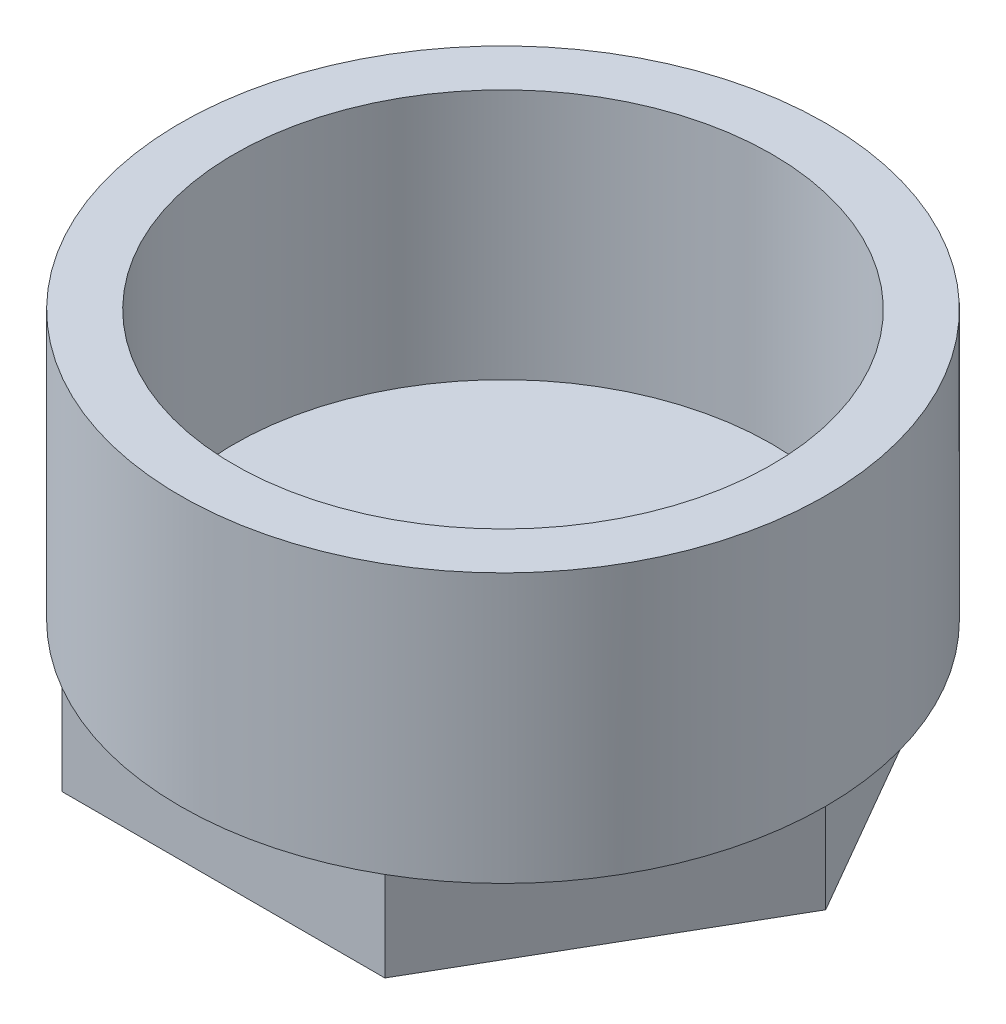
SolidWorks part; units mm, degrees
material "1.0035 (S185)"
ref_plane "Piano frontale" through (0, 0, 0) normal (0, 0, 1) x (1, 0, 0)
ref_plane "Piano superiore" through (0, 0, 0) normal (0, 1, 0) x (1, 0, 0)
ref_plane "Piano destro" through (0, 0, 0) normal (1, 0, 0) x (0, 0, -1)
sketch "Schizzo1" plane through (0, 0, 0) normal (0, 0, 1) x (1, 0, 0)
  line L0 (0, 0) -> (-18, 0)
  line L1 (-18, 0) -> (-18, 20)
  line L2 (-18, 20) -> (-15, 20)
  line L3 (-15, 20) -> (-15, 6)
  line L4 (-15, 6) -> (0, 6)
  line L5 (0, 6) -> (0, 0)
  line L6 (0, 0) -> (0, 10.8439) construction
  dimension "D1" = 36
  dimension "D2" = 30
  dimension "D3" = 6
  dimension "D4" = 20
revolve "Rivoluzione1" add sketch "Schizzo1" angle 360 about L6
sketch "Schizzo2" plane through (0, 0, 0) normal (0, -1, 0) x (1, 0, 0)
  circle A0 centre (0, 0) radius 1.585
  dimension "D1" = 3.17
extrude "Taglio-Estrusione1" cut sketch "Schizzo2" against normal blind 10
sketch "Schizzo3" plane through (0, 0, 0) normal (0, -1, 0) x (1, 0, 0)
  circle A0 centre (0, 0) radius 1.019
  circle A1 centre (0, 0) radius 1.5875
  dimension "D1" = 3.175
extrude "Estrusione-Estrusione1" [suppressed] add sketch "Schizzo3" along normal blind 8
sketch "Schizzo4" plane through (0, 0, 0) normal (0, 0, 1) x (1, 0, 0)
  line L0 (0, 0) -> (0, -9.8437)
sketch "Schizzo5" plane through (0, 0, 0) normal (0, -1, 0) x (-1, 0, 0)
  line L0 (9, 15.5885) -> (18, 0)
  line L1 (18, 0) -> (9, -15.5885)
  line L2 (9, -15.5885) -> (-9, -15.5885)
  line L3 (-9, -15.5885) -> (-18, 0)
  line L4 (-18, 0) -> (-9, 15.5885)
  line L5 (-9, 15.5885) -> (9, 15.5885)
  circle A0 centre (0, 0) radius 18 construction
  circle A1 centre (0, 0) radius 15
  circle M9 centre (0, 0) radius 18
extrude "Taglio-Estrusione2" cut sketch "Schizzo5" against normal blind 5 contours L5 M9 | L0 M9 | L1 M9 | L2 M9 | L3 M9 | L4 M9 region at (-14.3404, 0, -8.2794) region at (0, 0, -16.5588) region at (-14.3404, 0, 8.2794) region at (14.3404, 0, -8.2794) region at (0, 0, 16.5588) region at (14.3404, 0, 8.2794)
